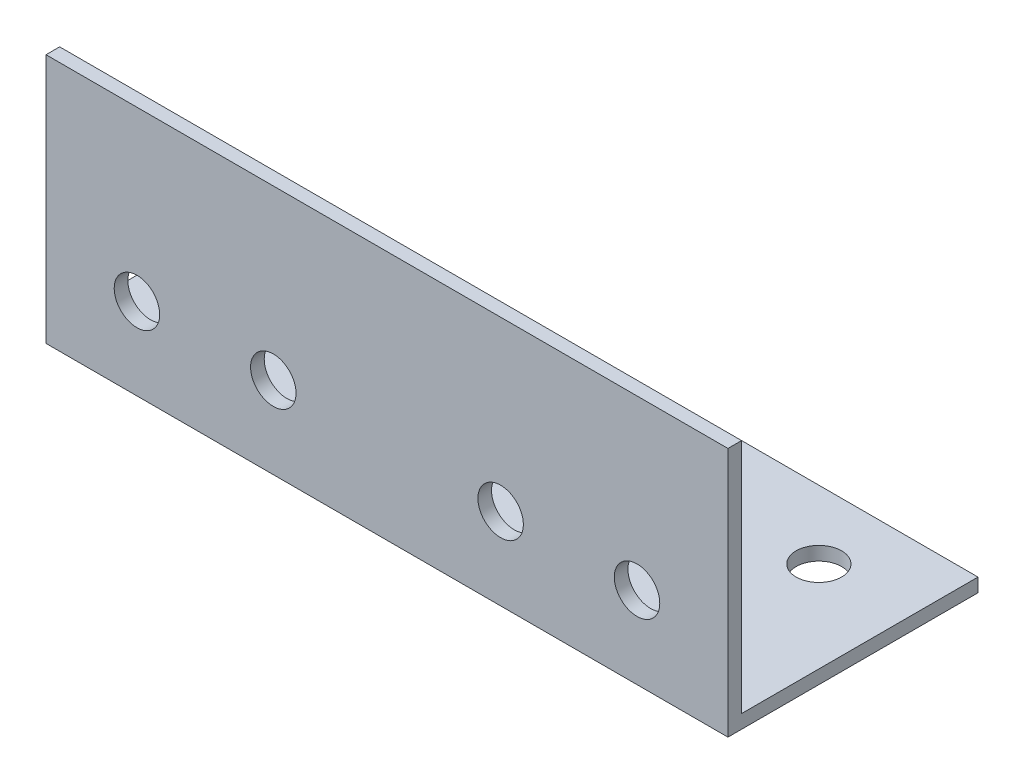
SolidWorks part; units mm, degrees
ref_plane "Спереди" through (0, 0, 0) normal (0, 0, 1) x (1, 0, 0)
ref_plane "Сверху" through (0, 0, 0) normal (0, 1, 0) x (1, 0, 0)
ref_plane "Справа" through (0, 0, 0) normal (1, 0, 0) x (0, 0, -1)
sketch "Эскиз1" plane through (0, 0, 0) normal (1, 0, 0) x (0, 0, -1)
  line L0 (0, 0) -> (0, 55)
  line L1 (0, 0) -> (55, 0)
extrude "Вытянуть-Тонкостенный1" add sketch "Эскиз1" along normal blind 150 thin thin type one direction reverse wall 3
sketch "Эскиз2" plane through (0, 0, 0) normal (0, -1, 0) x (1, 0, 0)
  line L0 (75, -58.7293) -> (75, -21.2393) construction
  circle A0 centre (130, -40) radius 5
  circle A1 centre (100, -40) radius 5
  circle A2 centre (50, -40) radius 5
  circle A3 centre (20, -40) radius 5
  dimension "D1" = 2
extrude "Вырез-Вытянуть1" cut sketch "Эскиз2" against normal through all
sketch "Эскиз3" plane through (0, 0, 0) normal (0, 0, 1) x (1, 0, 0)
  line L0 (75, 55) -> (75, 0) construction
  line L1 (150, 55) -> (0, 55) construction
  circle A0 centre (130, 18) radius 5
  circle A1 centre (100, 18) radius 5
  circle A2 centre (50, 18) radius 5
  circle A3 centre (20, 18) radius 5
  dimension "D1" = 2
extrude "Вырез-Вытянуть3" cut sketch "Эскиз3" against normal through all
